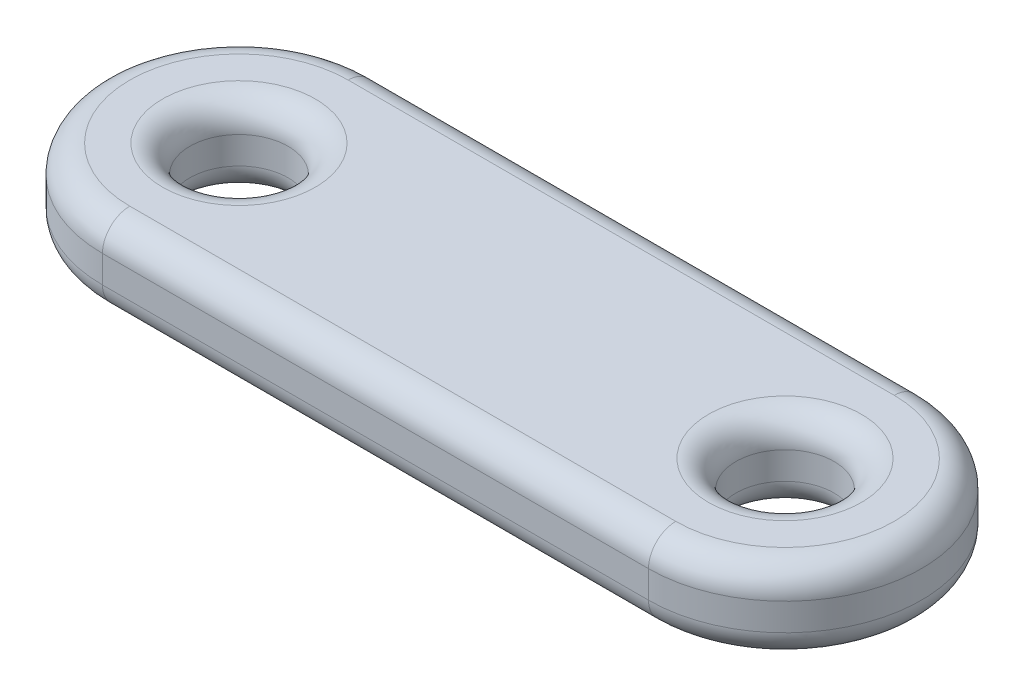
SolidWorks part; units mm, degrees
ref_plane "Front Plane" through (0, 0, 0) normal (0, 0, 1) x (1, 0, 0)
ref_plane "Top Plane" through (0, 0, 0) normal (0, 1, 0) x (1, 0, 0)
ref_plane "Right Plane" through (0, 0, 0) normal (1, 0, 0) x (0, 0, -1)
sketch "Sketch1" plane through (0, 0, 0) normal (0, 1, 0) x (1, 0, 0)
  line L0 (-10, 0) -> (10, 0) construction
  line L1 (-10, 5) -> (10, 5)
  line L2 (-10, -5) -> (10, -5)
  arc A0 (-10, 5) -> (-10, -5) centre (-10, 0) ccw
  arc A1 (10, -5) -> (10, 5) centre (10, 0) ccw
  point P3 (0, 0)
  dimension "D1" = 20
  dimension "D2" = 10
extrude "Boss-Extrude1" add sketch "Sketch1" along normal blind 3
hole_wizard "M3 Clearance Hole1" positions "3DSketch1" profile "Sketch2" hole size "M3" standard "ANSI Metric" end condition through all
sketch3d "3DSketch1"
  line L0 (-10, 3, 0) -> (-10, 0, 0) construction
  line L1 (10, 3, -5) -> (-10, 3, -5) construction
  point P0 (-10, 3, 0)
  point P4 (10, 3, 0)
  point P11 (0, 0, 0)
  point P22 (0, 0, 0)
  point P23 (0, 0, 0)
  dimension "D3" = 20
  dimension "D1" = 5
  dimension "D2" = 5
sketch "Sketch2" plane through (-10, 3, 0) normal (1, 0, 0) x (0, 0, 1)
  line L0 (0, 0) -> (0, 3)
  line L1 (0, 3) -> (1.8, 3)
  line L2 (1.8, 3) -> (1.8, 0)
  line L5 (1.8, 0) -> (0, 0)
  line L11 (0, -6.35) -> (0, 107.95) construction
  dimension "Thru Hole Dia." = 3.6
  dimension "Thru Hole Depth" = 3
fillet "Fillet1" radius 1 12 edges at (0, 0, 5) (15, 0, 0) (0, 0, -5) (-15, 0, 0) (10, 0, 1.8) (-10, 0, 1.8) (0, 3, -5) (15, 3, 0) (0, 3, 5) (-15, 3, 0) (10, 3, 1.8) (-10, 3, 1.8)
